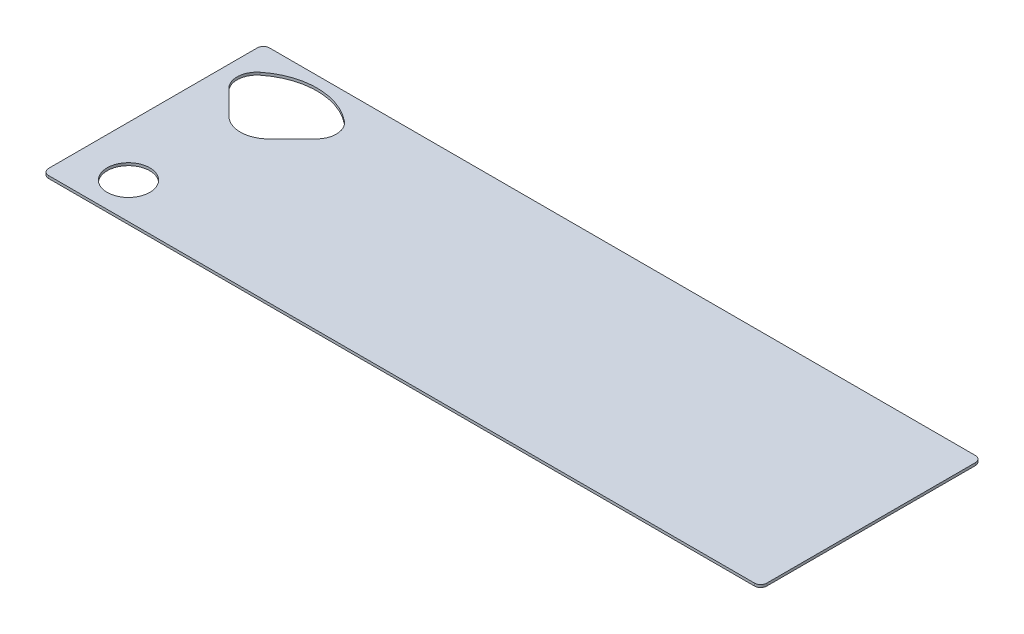
SolidWorks part; units mm, degrees
ref_plane "Front Plane" through (0, 0, 0) normal (0, 0, 1) x (1, 0, 0)
ref_plane "Top Plane" through (0, 0, 0) normal (0, 1, 0) x (1, 0, 0)
ref_plane "Right Plane" through (0, 0, 0) normal (1, 0, 0) x (0, 0, -1)
ref_axis "Axis1" through (0, -55, 0) along (0, 1, 0)
sketch "Sketch1" plane through (0, 0, 0) normal (0, 1, 0) x (1, 0, 0)
  line L10 (-861.6949, -269.7613) -> (861.6949, -269.7613)
  line L11 (876.8213, -254.6349) -> (876.8213, 254.6349)
  line L12 (861.6949, 269.7613) -> (-861.6949, 269.7613)
  line L13 (-876.8213, 254.6349) -> (-876.8213, -254.6349)
  line L14 (-861.6949, -269.7613) -> (861.6949, -269.7613)
  line L15 (876.8213, -254.6349) -> (876.8213, 254.6349)
  line L16 (861.6949, 269.7613) -> (-861.6949, 269.7613)
  line L17 (-876.8213, 254.6349) -> (-876.8213, -254.6349)
  ellipse E4 centre (861.4669, -254.4069) end of major axis (872.4044, -265.3444) minor radius 15.24 (861.6949, -269.7613) -> (876.8213, -254.6349) ccw
  ellipse E5 centre (861.4669, 254.4069) end of major axis (872.4044, 265.3444) minor radius 15.24 (876.8213, 254.6349) -> (861.6949, 269.7613) ccw
  ellipse E6 centre (-861.4669, 254.4069) end of major axis (-872.4044, 265.3444) minor radius 15.24 (-861.6949, 269.7613) -> (-876.8213, 254.6349) ccw
  ellipse E7 centre (-861.4669, -254.4069) end of major axis (-872.4044, -265.3444) minor radius 15.24 (-876.8213, -254.6349) -> (-861.6949, -269.7613) ccw
  ellipse E8 centre (861.4669, -254.4069) end of major axis (872.4044, -265.3444) minor radius 15.24 (861.6949, -269.7613) -> (876.8213, -254.6349) ccw
  ellipse E9 centre (861.4669, 254.4069) end of major axis (872.4044, 265.3444) minor radius 15.24 (876.8213, 254.6349) -> (861.6949, 269.7613) ccw
  ellipse E10 centre (-861.4669, 254.4069) end of major axis (-872.4044, 265.3444) minor radius 15.24 (-861.6949, 269.7613) -> (-876.8213, 254.6349) ccw
  ellipse E11 centre (-861.4669, -254.4069) end of major axis (-872.4044, -265.3444) minor radius 15.24 (-876.8213, -254.6349) -> (-861.6949, -269.7613) ccw
  dimension "D1" = 0
extrude "Boss-Extrude1" add sketch "Sketch1" along normal blind 6.35
sketch "Sketch2" plane through (0, 6.35, 0) normal (0, 1, 0) x (1, 0, 0)
  line L4 (-825.9543, 134.5915) -> (-767.5663, 76.2035)
  line L5 (-670.5694, 76.2035) -> (-612.1814, 134.5915)
  line L6 (-825.9543, 134.5915) -> (-767.5663, 76.2035)
  line L7 (-670.5694, 76.2035) -> (-612.1814, 134.5915)
  arc A8 (-767.5663, 76.2035) -> (-670.5694, 76.2035) centre (-719.0679, 124.7019) ccw
  arc A9 (-822.0432, 206.8134) -> (-825.9543, 134.5915) centre (-791.598, 168.9478) ccw
  arc A10 (-616.0925, 206.8134) -> (-822.0432, 206.8134) centre (-719.0679, 78.74) ccw
  arc A11 (-612.1814, 134.5915) -> (-616.0925, 206.8134) centre (-646.5378, 168.9478) ccw
  arc A12 (-767.5663, 76.2035) -> (-670.5694, 76.2035) centre (-719.0679, 124.7019) ccw
  arc A13 (-822.0432, 206.8134) -> (-825.9543, 134.5915) centre (-791.598, 168.9478) ccw
  arc A14 (-616.0925, 206.8134) -> (-822.0432, 206.8134) centre (-719.0679, 78.74) ccw
  arc A15 (-612.1814, 134.5915) -> (-616.0925, 206.8134) centre (-646.5378, 168.9478) ccw
  dimension "D1" = 15.24
extrude "Cut-Extrude1" cut sketch "Sketch2" against normal through all
sketch "Sketch3" plane through (0, 6.35, 0) normal (0, 1, 0) x (1, 0, 0)
  circle A2 centre (-754.5064, -181.8446) radius 52.07
  circle A3 centre (-754.5064, -181.8446) radius 52.07
  dimension "D1" = 15.24
extrude "Cut-Extrude2" cut sketch "Sketch3" against normal through all
